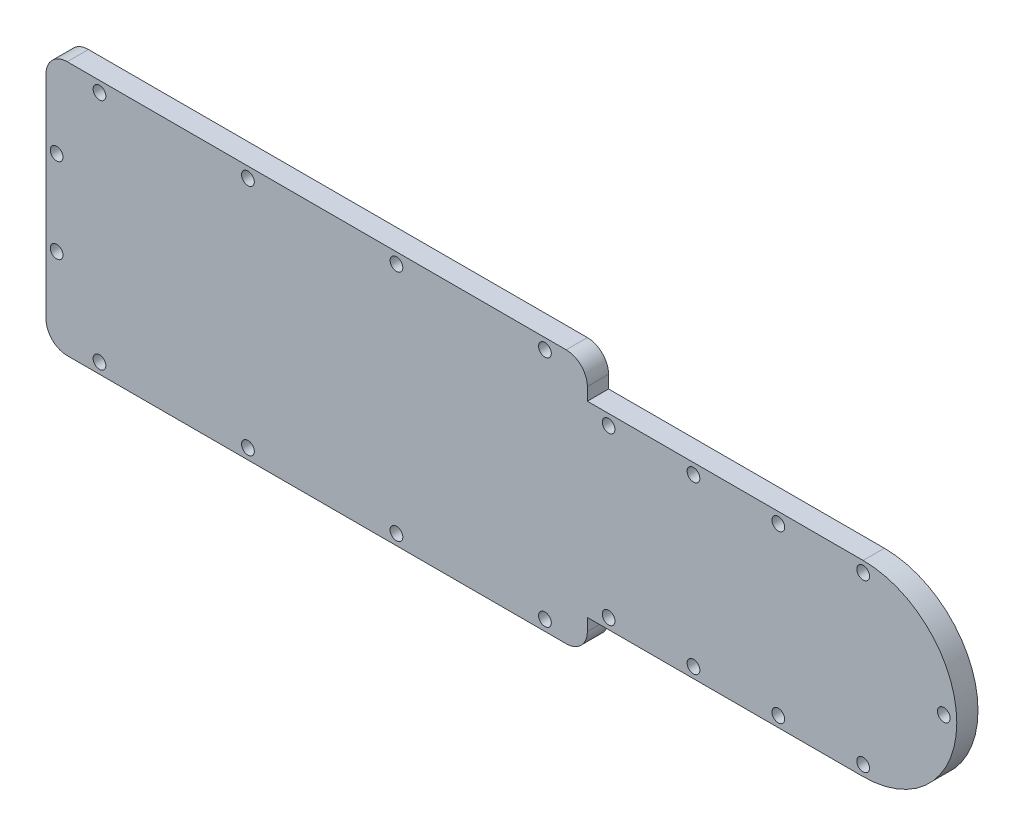
SolidWorks part; units mm, degrees
material "ABS"
ref_plane "Front Plane" through (0, 0, 0) normal (0, 0, 1) x (1, 0, 0)
ref_plane "Top Plane" through (0, 0, 0) normal (0, 1, 0) x (1, 0, 0)
ref_plane "Right Plane" through (0, 0, 0) normal (1, 0, 0) x (0, 0, -1)
sketch "Sketch1" plane through (0, 0, 0) normal (0, 0, 1) x (1, 0, 0)
  line L0 (63.8, 22) -> (128.81, 22)
  line L1 (-58.8, -30) -> (58.8, -30)
  line L2 (-63.8, -25) -> (-63.8, 25)
  line L3 (-58.8, 30) -> (58.8, 30)
  line L4 (63.8, -25) -> (63.8, 25)
  line L5 (-63.8, -30) -> (63.8, 30) construction
  line L6 (-63.8, 30) -> (63.8, -30) construction
  line L7 (63.8, -22.136) -> (128.81, -22.136)
  arc A0 (-63.8, -25) -> (-58.8, -30) centre (-58.8, -25) ccw
  arc A1 (58.8, -30) -> (63.8, -25) centre (58.8, -25) ccw
  arc A2 (63.8, 25) -> (58.8, 30) centre (58.8, 25) ccw
  arc A3 (-58.8, 30) -> (-63.8, 25) centre (-58.8, 25) ccw
  arc A5 (128.81, 22) -> (128.81, -22.136) centre (128.81, -0.068) cw
  point P0 (0, 0)
  dimension "D2" = 5
  dimension "D1" = 60
  dimension "D3" = 117.6
extrude "Boss-Extrude1" add sketch "Sketch1" along normal blind 5 contours A5 L0 L4 L7 | L3 A3 L2 A0 L1 A1 L4 A2 region at (105.1184, -0.068, 0) region at (0, 0, 0)
sketch "Sketch2" plane through (0, 0, 5) normal (0, 0, 1) x (1, 0, 0)
  line L8 (-63.8, -25) -> (-63.8, 25) construction
  line L9 (-58.8, 30) -> (58.8, 30) construction
  circle A5 centre (-51.2, 27.5) radius 1.5
  circle A6 centre (-61.3, 10) radius 1.5
  dimension "D3" = 3
  dimension "D6" = 3
  dimension "D4" = 12.6
  dimension "D5" = 2.5
  dimension "D7" = 2.5
  dimension "D8" = 20
sketch "Sketch4" plane through (0, 0, 5) normal (0, 0, 1) x (1, 0, 0)
  line L0 (63.8, 22) -> (128.81, 22) construction
  circle A0 centre (68.81, 19.5) radius 1.5
  arc A1 (128.81, -22.136) -> (128.81, 22) centre (128.81, -0.068) ccw construction
  circle A2 centre (88.81, 19.5) radius 1.5
  circle A3 centre (108.81, 19.5) radius 1.5
  circle A4 centre (128.81, 19.5) radius 1.5
  circle A5 centre (88.81, -19.66) radius 1.5
  circle A6 centre (108.81, -19.66) radius 1.5
  circle A7 centre (128.81, -19.66) radius 1.5
  circle A8 centre (68.81, -19.66) radius 1.5
  circle A9 centre (147.81, 0) radius 1.5
  dimension "D1" = 3
  dimension "D2" = 2.5
  dimension "D3" = 60
  dimension "D6" = 3
  dimension "D8" = 22
  dimension "D7" = 19
  dimension "D4" = 4
  dimension "D5" = 2
extrude "Cut-Extrude3" cut sketch "Sketch4" against normal through all
extrude "Cut-Extrude4" cut sketch "Sketch2" against normal through all
pattern_linear "LPattern1" count 4 spacing 35 along (1, 0, 0) count 2 spacing 55 along (0, -1, 0) of face at (-49.7, 27.5, 0)
pattern_linear "LPattern2" count 2 spacing 20 along (0, -1, 0) of face at (-59.8, 10, 0)
